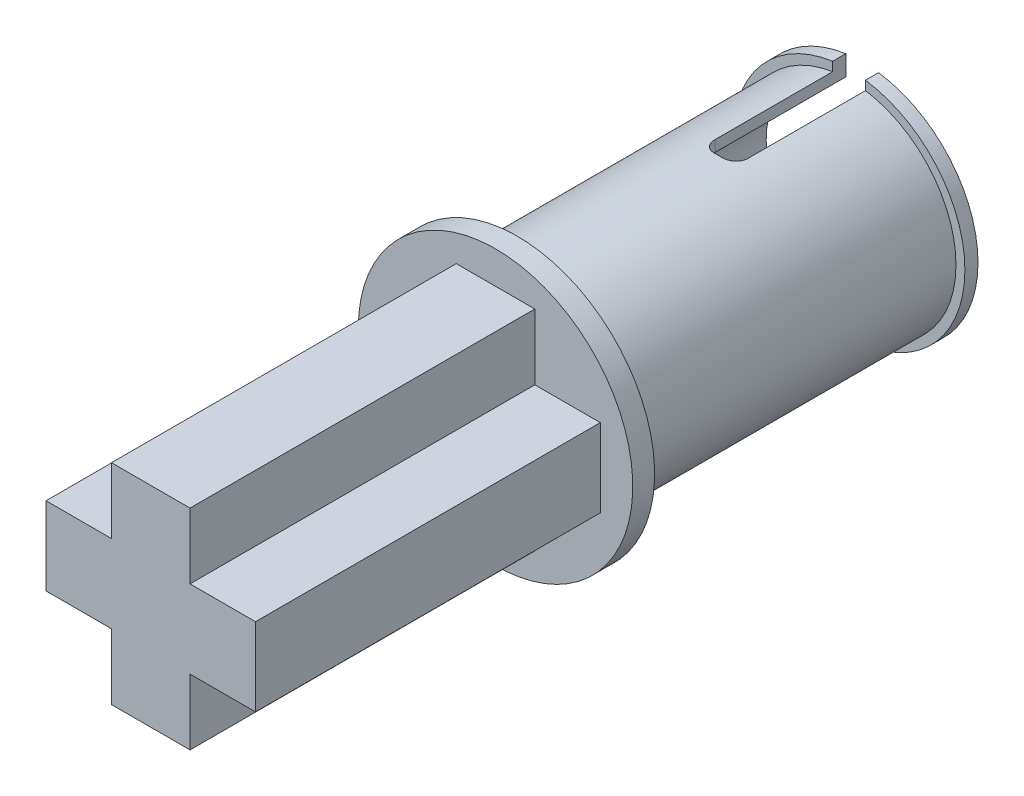
SolidWorks part; units mm, degrees
ref_plane "Front Plane" through (0, 0, 0) normal (0, 0, 1) x (1, 0, 0)
ref_plane "Top Plane" through (0, 0, 0) normal (0, 1, 0) x (1, 0, 0)
ref_plane "Right Plane" through (0, 0, 0) normal (1, 0, 0) x (0, 0, -1)
sketch "Sketch1" plane through (0, 0, 0) normal (0, 0, 1) x (1, 0, 0)
  line L0 (-2.4, 0) -> (2.4, 0)
  line L1 (-2.4, 0.895) -> (-2.4, -0.895)
  line L2 (-2.4, 0.895) -> (-0.9, 0.895)
  line L3 (0, 2.4) -> (0, -2.4)
  line L4 (-0.9, 0.895) -> (-0.9, 2.4)
  line L5 (-0.9, 2.4) -> (0.9, 2.4)
  line L6 (0.9, 0.895) -> (0.9, 2.4)
  line L7 (2.4, 0.895) -> (0.9, 0.895)
  line L8 (2.4, 0.895) -> (2.4, -0.895)
  line L9 (2.4, -0.895) -> (0.9, -0.895)
  line L10 (0.9, -0.895) -> (0.9, -2.4)
  line L11 (-0.9, -2.4) -> (0.9, -2.4)
  line L12 (-0.9, -0.895) -> (-0.9, -2.4)
  line L13 (-2.4, -0.895) -> (-0.9, -0.895)
  point P4 (0, 0)
  point P8 (-2.4, 0)
  point P12 (0, 0)
  dimension "D1" = 4.8
  dimension "D2" = 1.79
  dimension "D3" = 1.5
  dimension "D4" = 4.8
extrude "Boss-Extrude1" add sketch "Sketch1" along normal blind 7.9 contours L5 L4 L2 L1 L0 L3 | L1 L13 L12 L11 L3 L0 | L8 L7 L6 L5 L3 L0 | L3 L11 L10 L9 L8 L0 region at (-2.3661, 0.4475, 0) region at (-1.2, -0.0339, 0) region at (0.0339, 1.2, 0) region at (1.2, -0.0339, 0)
sketch "Sketch2" plane through (0, 0, 0) normal (0, 0, -1) x (-1, 0, 0)
  circle A0 centre (0, 0) radius 3.1445
extrude "Boss-Extrude3" add sketch "Sketch2" along normal blind 0.5 contours A0
sketch "Sketch3" plane through (0, 0, -0.5) normal (0, 0, -1) x (-1, 0, 0)
  circle A0 centre (0, 0) radius 2.45
  dimension "D1" = 4.9
extrude "Boss-Extrude4" add sketch "Sketch3" along normal blind 7.9
sketch "Sketch4" plane through (0, 0, -8.4) normal (0, 0, -1) x (-1, 0, 0)
  circle A0 centre (0, 0) radius 2.6546
extrude "Boss-Extrude5" add sketch "Sketch4" against normal blind 0.3
sketch "Sketch5" plane through (0, 0, -8.4) normal (0, 0, -1) x (-1, 0, 0)
  circle A0 centre (0, 0) radius 2.1986
extrude "Cut-Extrude1" cut sketch "Sketch5" against normal up to surface (7.9 mm away) up to face at (-2.45, 0, -0.5)
sketch "Sketch6" plane through (0, 0, -8.4) normal (0, 0, -1) x (-1, 0, 0)
  line L0 (0, 0) -> (2.6546, 0) construction
  line L1 (0, 0) -> (0, 2.6546) construction
  line L2 (0.3755, 2.6546) -> (0.3755, 2.1663)
  line L3 (0.3755, 2.6546) -> (-0.3755, 2.6546)
  line L4 (0, 2.6546) -> (0, 2.1663)
  line L5 (0.3755, 2.1663) -> (-0.3755, 2.1663)
  line L6 (-0.3755, 2.6546) -> (-0.3755, 2.1663)
  line L7 (0.3755, -2.6546) -> (0.3755, -2.1663)
  line L8 (0.3755, -2.6546) -> (-0.3755, -2.6546)
  line L9 (-0.3755, -2.6546) -> (-0.3755, -2.1663)
  line L10 (0.3755, -2.1663) -> (-0.3755, -2.1663)
  circle A0 centre (0, 0) radius 2.6546 construction
  circle A1 centre (0, 0) radius 2.1986 construction
  circle M8 centre (0, 0) radius 2.1986
  circle M9 centre (0, 0) radius 2.6546
extrude "Cut-Extrude2" cut sketch "Sketch6" against normal blind 3.3 contours L4 L2 M9 M8 | L6 L4 M9 M8 | L9 L7 M9 M8 region at (-0.1881, 2.4168, -8.4) region at (0.1881, 2.4168, -8.4) region at (0, -2.4168, -8.4)
fillet "Fillet1" radius 0.3 4 edges at (-0.3755, -2.2937, -5.1) (0.3755, -2.2937, -5.1) (-0.3755, 2.2937, -5.1) (0.3755, 2.2937, -5.1)
